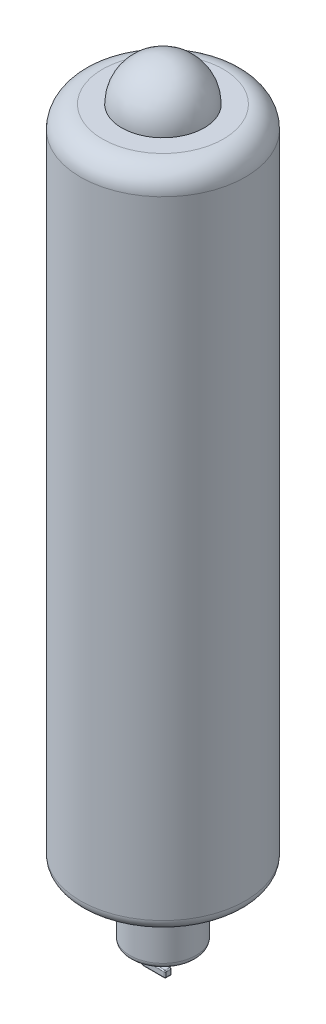
SolidWorks part; units mm, degrees
material "Ceramic Porcelain"
ref_plane "Front Plane" through (0, 0, 0) normal (0, 0, 1) x (1, 0, 0)
ref_plane "Top Plane" through (0, 0, 0) normal (0, 1, 0) x (1, 0, 0)
ref_plane "Right Plane" through (0, 0, 0) normal (1, 0, 0) x (0, 0, -1)
sketch "Sketch1" plane through (0, 0, 0) normal (0, 1, 0) x (1, 0, 0)
  circle A0 centre (0, 0) radius 7.5
  dimension "D1" = 15
extrude "Boss-Extrude1" add sketch "Sketch1" along normal blind 60
sketch "Sketch2" plane through (0, 60, 0) normal (0, 1, 0) x (1, 0, 0)
  circle A0 centre (0, 0) radius 3.75
  dimension "D1" = 7.5
extrude "Boss-Extrude2" add sketch "Sketch2" along normal blind 3.75
fillet "Fillet1" radius 3.75 1 edges at (0, 63.75, 3.75)
fillet "Fillet2" radius 2 1 edges at (0, 60, 7.5)
fillet "Fillet3" radius 1 1 edges at (0, 0, 7.5)
sketch "Sketch3" plane through (0, 0, 0) normal (0, -1, 0) x (1, 0, 0)
  circle A0 centre (0, 0) radius 3
  dimension "D1" = 6
extrude "Boss-Extrude3" add sketch "Sketch3" along normal blind 6.05
fillet "Fillet4" radius 0.5 1 edges at (0, -6.05, -3)
sketch "Sketch4" plane through (0, 0, 0) normal (0, 0, 1) x (1, 0, 0)
  line L0 (-2.5, -6.05) -> (2.5, -6.05) construction
  line L1 (0, -6.05) -> (0.5, -6.05)
  line L2 (0, -6.05) -> (0, -7.2)
  line L3 (0, -7.2) -> (0.5, -7.2)
  line L4 (0.5, -6.05) -> (0.5, -7.2)
  line L5 (0.5, -7.2) -> (0.5, -8.5) construction
  line L6 (0.5, -8.5) -> (-1.4, -8.5)
  line L7 (-2, -7.9) -> (-2, -6.05)
  line L8 (-2, -6.05) -> (-1.4, -6.05)
  line L9 (-1.4, -6.05) -> (-1.4, -7.5)
  line L10 (-1, -7.9) -> (0.5, -7.9)
  line L11 (0.5, -7.9) -> (0.5, -8.5)
  arc A0 (-1.4, -8.5) -> (-2, -7.9) centre (-1.4, -7.9) cw
  arc A1 (-1.4, -7.5) -> (-1, -7.9) centre (-1, -7.5) ccw
  dimension "D4" = 0.4
  dimension "D6" = 0.6
  dimension "D1" = 0.5
  dimension "D2" = 2.45
  dimension "D3" = 1.4
  dimension "D5" = 0.7
  dimension "D7" = 0.6
extrude "Boss-Extrude4" add sketch "Sketch4" along normal mid plane 0.6
fillet "Fillet5" radius 0.1 24 edges at (-2, -6.975, 0.3) (-1.8243, -8.3243, 0.3) (-2, -6.975, -0.3) (-1.8243, -8.3243, -0.3) (-0.25, -7.9, -0.3) (-1.2828, -7.7828, -0.3) (-0.25, -7.9, 0.3) (-1.2828, -7.7828, 0.3) (0, -7.2, 0) (0.25, -7.2, 0.3) (0.5, -7.2, 0) (0.25, -7.2, -0.3) (-0.45, -8.5, 0.3) (-0.45, -8.5, -0.3) (0.5, -8.5, 0) (0.5, -8.2, 0.3) (0.5, -7.9, 0) (0.5, -8.2, -0.3) (0, -6.625, -0.3) (0, -6.625, 0.3) (0.5, -6.625, -0.3) (0.5, -6.625, 0.3) (-1.4, -6.775, -0.3) (-1.4, -6.775, 0.3)
fillet "Fillet6" radius 0.06 16 edges at (0.4707, -6.05, -0.2707) (0.5, -6.05, 0) (0.4707, -6.05, 0.2707) (0.25, -6.05, 0.3) (0.0293, -6.05, 0.2707) (0, -6.05, 0) (0.0293, -6.05, -0.2707) (-1.4293, -6.05, -0.2707) (-1.4, -6.05, 0) (-1.4293, -6.05, 0.2707) (-1.7, -6.05, 0.3) (-1.9707, -6.05, 0.2707) (-2, -6.05, 0) (-1.9707, -6.05, -0.2707) (0.25, -6.05, -0.3) (-1.7, -6.05, -0.3)
